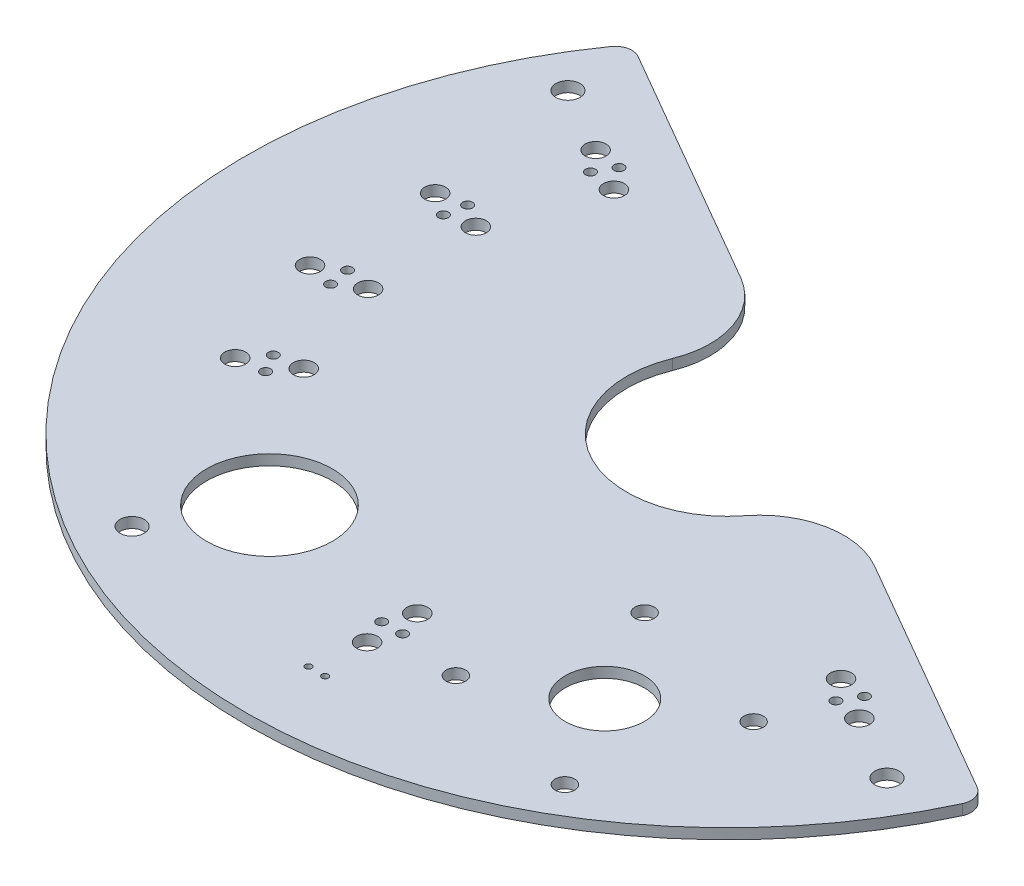
SolidWorks part; units mm, degrees
ref_plane "Front Plane" through (0, 0, 0) normal (0, 0, 1) x (1, 0, 0)
ref_plane "Top Plane" through (0, 0, 0) normal (0, 1, 0) x (1, 0, 0)
ref_plane "Right Plane" through (0, 0, 0) normal (1, 0, 0) x (0, 0, -1)
sketch "Sketch1" plane through (0, 0, 0) normal (0, 1, 0) x (1, 0, 0)
  line L0 (0, 50.8) -> (0, 59.6199) construction
  line L1 (0, 50.8) -> (11.3081, 50.8) construction
  line L2 (0, 0) -> (0, 47) construction
  line L3 (0, 0) -> (-46.286, 8.1615) construction
  line L4 (0, 0) -> (0, 47) construction
  line L5 (0, 0) -> (-46.286, -8.1615) construction
  circle A0 centre (0, 0) radius 50.8 construction
  circle A1 centre (0, 0) radius 15.24
  circle A2 centre (0, 0) radius 73.025
  circle A3 centre (0, 50.8) radius 6.3 construction
  circle A4 centre (25.4, 43.9941) radius 6.3 construction
  circle A5 centre (43.9941, 25.4) radius 6.3 construction
  circle A6 centre (50.8, 0) radius 6.3 construction
  circle A7 centre (43.9941, -25.4) radius 6.3 construction
  circle A8 centre (25.4, -43.9941) radius 6.3 construction
  circle A9 centre (0, -50.8) radius 6.3 construction
  circle A10 centre (-25.4, -43.9941) radius 6.3 construction
  circle A11 centre (-43.9941, -25.4) radius 6.3 construction
  circle A12 centre (-50.8, 0) radius 6.3 construction
  circle A13 centre (-43.9941, 25.4) radius 6.3 construction
  circle A14 centre (-25.4, 43.9941) radius 6.3 construction
  circle A15 centre (0, 50.8) radius 1.585 construction
  circle A16 centre (-1.585, 50.8) radius 0.75
  circle A17 centre (1.585, 50.8) radius 0.75
  circle A18 centre (0, 50.8) radius 3.8 construction
  circle A19 centre (0, 54.6) radius 1.585
  circle A20 centre (0, 47) radius 1.585
  circle A21 centre (47.285, 27.3) radius 1.585
  circle A22 centre (43.2016, 26.7727) radius 0.75
  circle A23 centre (44.7866, 24.0273) radius 0.75
  circle A24 centre (40.7032, 23.5) radius 1.585
  circle A25 centre (47.285, -27.3) radius 1.585
  circle A26 centre (44.7866, -24.0273) radius 0.75
  circle A27 centre (43.2016, -26.7727) radius 0.75
  circle A28 centre (40.7032, -23.5) radius 1.585
  circle A29 centre (0, -54.6) radius 1.585
  circle A30 centre (1.585, -50.8) radius 0.75
  circle A31 centre (-1.585, -50.8) radius 0.75
  circle A32 centre (0, -47) radius 1.585
  circle A33 centre (-47.285, -27.3) radius 1.585
  circle A34 centre (-43.2016, -26.7727) radius 0.75
  circle A35 centre (-44.7866, -24.0273) radius 0.75
  circle A36 centre (-40.7032, -23.5) radius 1.585
  circle A37 centre (-47.285, 27.3) radius 1.585
  circle A38 centre (-44.7866, 24.0273) radius 0.75
  circle A39 centre (-43.2016, 26.7727) radius 0.75
  circle A40 centre (-40.7032, 23.5) radius 1.585
  circle A41 centre (25.4, 43.9941) radius 20
  circle A42 centre (-25.4, -43.9941) radius 9.525
  circle A43 centre (25.4, -43.9941) radius 6
  circle A44 centre (-46.286, 8.1615) radius 1.585
  circle A45 centre (-50.3035, 7.2604) radius 0.75
  circle A46 centre (-49.753, 10.3822) radius 0.75
  circle A47 centre (-53.7705, 9.4812) radius 1.585
  circle A48 centre (-46.286, -8.1615) radius 1.585
  circle A49 centre (-49.753, -10.3822) radius 0.75
  circle A50 centre (-50.3035, -7.2604) radius 0.75
  circle A51 centre (-53.7705, -9.4812) radius 1.585
  point P50 (0, 0)
  point P84 (0, 0)
  dimension "D1" = 12
  dimension "D2" = 101.6
  dimension "D3" = 3.17
  dimension "D4" = 1.5
  dimension "D5" = 7.6
  dimension "D6" = 6
  dimension "D7" = 3.17
  dimension "D8" = 40
  dimension "D9" = 19.05
  dimension "D10" = 12
  dimension "D11" = 146.05
  dimension "D12" = 30.48
  dimension "D14" = 80
  dimension "D16" = 100
  dimension "D13" = 2
  dimension "D15" = 2
extrude "Boss-Extrude1" add sketch "Sketch1" against normal blind 1.5875
sketch "Sketch2" plane through (0, 0, 0) normal (0, 1, 0) x (1, 0, 0)
  line L0 (0, 0) -> (0, 66.04) construction
  line L1 (0, 0) -> (-57.1923, 33.02) construction
  circle A0 centre (0, 0) radius 66.04 construction
  circle A1 centre (0, 66.04) radius 1.8288 construction
  circle A2 centre (-57.1923, 33.02) radius 1.8288
  circle A3 centre (33.02, 57.1923) radius 1.8288
  circle A4 centre (57.1923, -33.02) radius 1.8288
  circle A5 centre (-33.02, -57.1923) radius 1.8288
  point P17 (0, 0)
  dimension "D1" = 132.08
  dimension "D2" = 3.6576
  dimension "D3" = 2
  dimension "D4" = 60
  dimension "D5" = 4
extrude "Cut-Extrude1" cut sketch "Sketch2" against normal through all
sketch "Sketch3" plane through (0, 0, 0) normal (0, 1, 0) x (1, 0, 0)
  line L0 (-57.1923, 33.02) -> (57.1923, -33.02) construction
  line L1 (-59.5338, 44.6372) -> (68.4238, -29.2392)
  line L2 (-52.7473, 40.719) -> (61.6373, -25.321) construction
  arc A0 (68.4238, -29.2392) -> (-59.5338, 44.6372) centre (0, 0) ccw
  dimension "D1" = 8.89
extrude "Cut-Extrude2" cut sketch "Sketch3" against normal through all
fillet "Fillet1" radius 12.7 2 edges at (15.165, -0.7937, -1.5098) (-6.275, -0.7937, -13.8882)
fillet "Fillet2" radius 2.54 2 edges at (67.2161, -0.7937, 28.542) (-58.3261, -0.7937, -43.9399)
sketch "Sketch4" plane through (0, 0, 0) normal (0, 1, 0) x (1, 0, 0)
  line L0 (0, 0) -> (0, -73.025) construction
  arc A0 (-59.6949, 42.0615) -> (66.2738, -30.6666) centre (0, 0) ccw construction
  circle A1 centre (0, 0) radius 62.23 construction
  circle A2 centre (0, -62.23) radius 0.4953 construction
  circle A3 centre (1.27, -62.23) radius 0.4953
  circle A4 centre (-1.27, -62.23) radius 0.4953
  dimension "D1" = 0.9906
  dimension "D4" = 124.46
  dimension "D2" = 2
  dimension "D3" = 2
extrude "Cut-Extrude3" cut sketch "Sketch4" against normal through all
sketch "Sketch5" plane through (0, -1.5875, 0) normal (0, -1, 0) x (1, 0, 0)
  line L13 (30.4135, 24.5983) -> (41.5359, 31.0198)
  line L14 (28.0125, 9.134) -> (57.5769, 26.203)
  line L29 (46.7892, 22.3211) -> (54.9392, 27.0264)
  line L30 (29.0803, 12.0968) -> (45.0238, 21.3018)
  line L31 (6.096, 38.6381) -> (6.096, 51.4811)
  line L32 (29.8903, 21.9498) -> (40.9598, 28.3409)
  line L33 (-6.096, 38.6381) -> (-6.096, 51.4811)
  line L34 (4.064, 36.8606) -> (4.064, 49.6426)
  line L35 (-21.9165, -19.6925) -> (-41.5359, -31.0198)
  line L39 (-4.064, 36.8606) -> (-4.064, 49.6426)
  line L40 (-30.4135, 24.5983) -> (-41.5359, 31.0198)
  line L42 (-29.8903, 21.9498) -> (-40.9598, 28.3409)
  line L93 (-25.0163, -19.1359) -> (-40.9598, -28.3409)
  line L98 (-46.7892, 22.3211) -> (-54.9392, 27.0264)
  line L99 (-47.6319, 20.4612) -> (-57.5769, 26.203)
  arc A0 (1.2907, 63.2458) -> (1.2493, 61.2142) centre (1.27, 62.23) ccw
  arc A1 (-1.2493, 61.2142) -> (-1.2907, 63.2458) centre (-1.27, 62.23) ccw
  arc A2 (-1.2493, 61.2142) -> (-54.9392, 27.0264) centre (0, 0) ccw
  arc A3 (-1.2907, 63.2458) -> (-57.5769, 26.203) centre (0, 0) ccw
  arc A4 (54.9392, 27.0264) -> (1.2493, 61.2142) centre (0, 0) ccw
  arc A6 (6.096, 51.4811) -> (2.3857, 51.7858) centre (0, 0) ccw
  arc A7 (29.8903, 21.9498) -> (4.064, 36.8606) centre (0, 0) ccw
  arc A8 (2.3857, 51.7858) -> (2.3071, 49.7553) centre (1.585, 50.8) ccw
  arc A9 (-2.3071, 49.7553) -> (-2.3857, 51.7858) centre (-1.585, 50.8) ccw
  arc A10 (-48.5987, -10.912) -> (-50.5848, -11.342) centre (-49.753, -10.3822) ccw
  arc A11 (-51.4133, -6.6431) -> (-49.4, -6.3679) centre (-50.3035, -7.2604) ccw
  arc A12 (46.0407, 23.8268) -> (44.2429, 22.8796) centre (44.7866, 24.0273) ccw
  arc A13 (41.9358, 26.8756) -> (43.655, 27.959) centre (43.2016, 26.7727) ccw
  arc A14 (-49.4, 6.3679) -> (-51.4133, 6.6431) centre (-50.3035, 7.2604) ccw
  arc A15 (-50.5848, 11.342) -> (-48.5987, 10.912) centre (-49.753, 10.3822) ccw
  arc A16 (57.5769, 26.203) -> (1.2907, 63.2458) centre (0, 0) ccw
  arc A17 (-2.3857, 51.7858) -> (-6.096, 51.4811) centre (0, 0) ccw
  arc A18 (-2.3071, 49.7553) -> (-4.064, 49.6426) centre (0, 0) ccw
  arc A19 (45.0238, 21.3018) -> (44.2429, 22.8796) centre (0, 0) ccw
  arc A20 (29.0803, 12.0968) -> (-25.0163, -19.1359) centre (0, 0) ccw
  arc A21 (28.0125, 9.134) -> (-21.9165, -19.6925) centre (0, 0) ccw
  arc A22 (46.7892, 22.3211) -> (46.0407, 23.8268) centre (0, 0) ccw
  arc A23 (43.655, 27.959) -> (41.5359, 31.0198) centre (0, 0) ccw
  arc A24 (-46.0407, -23.8268) -> (-44.2429, -22.8796) centre (-44.7866, -24.0273) ccw
  arc A25 (-41.9358, -26.8756) -> (-43.655, -27.959) centre (-43.2016, -26.7727) ccw
  arc A26 (41.9358, 26.8756) -> (40.9598, 28.3409) centre (0, 0) ccw
  circle A27 centre (1.27, 62.23) radius 0.4953
  arc A28 (-43.655, 27.959) -> (-41.9358, 26.8756) centre (-43.2016, 26.7727) ccw
  arc A29 (-44.2429, 22.8796) -> (-46.0407, 23.8268) centre (-44.7866, 24.0273) ccw
  circle A30 centre (-1.27, 62.23) radius 0.4953
  arc A31 (-43.655, -27.959) -> (-41.5359, -31.0198) centre (0, 0) ccw
  circle A32 centre (-26.7727, 43.2016) radius 1.27 [skipped]
  circle A33 centre (-24.0273, 44.7866) radius 1.27 [skipped]
  circle A34 centre (24.0273, 44.7866) radius 1.27 [skipped]
  circle A35 centre (26.7727, 43.2016) radius 1.27 [skipped]
  circle A36 centre (50.8, 1.585) radius 1.27 [skipped]
  circle A37 centre (50.8, -1.585) radius 1.27 [skipped]
  circle A38 centre (44.7866, -24.0273) radius 1.27 [skipped]
  circle A39 centre (43.2016, -26.7727) radius 1.27 [skipped]
  circle A40 centre (26.7727, -43.2016) radius 1.27 [skipped]
  circle A41 centre (24.0273, -44.7866) radius 1.27 [skipped]
  circle A42 centre (1.585, -50.8) radius 1.27 [skipped]
  circle A43 centre (-1.585, -50.8) radius 1.27 [skipped]
  circle A44 centre (-24.0273, -44.7866) radius 1.27 [skipped]
  circle A45 centre (-26.7727, -43.2016) radius 1.27 [skipped]
  circle A46 centre (-50.8, 1.585) radius 1.27 [skipped]
  circle A47 centre (-50.8, -1.585) radius 1.27 [skipped]
  arc A48 (-41.9358, -26.8756) -> (-40.9598, -28.3409) centre (0, 0) ccw
  arc A49 (-40.9598, 28.3409) -> (-41.9358, 26.8756) centre (0, 0) ccw
  arc A50 (30.4135, 24.5983) -> (6.096, 38.6381) centre (0, 0) ccw
  circle A51 centre (1.585, 50.8) radius 0.75
  arc A52 (-46.0407, 23.8268) -> (-46.7892, 22.3211) centre (0, 0) ccw
  arc A53 (4.064, 49.6426) -> (2.3071, 49.7553) centre (0, 0) ccw
  arc A54 (-41.5359, 31.0198) -> (-43.655, 27.959) centre (0, 0) ccw
  arc A55 (-6.096, 38.6381) -> (-30.4135, 24.5983) centre (0, 0) ccw
  arc A56 (-4.064, 36.8606) -> (-29.8903, 21.9498) centre (0, 0) ccw
  arc A57 (-44.2429, 22.8796) -> (-48.5987, 10.912) centre (0, 0) ccw
  circle A58 centre (-1.585, 50.8) radius 0.75
  circle A59 centre (43.2016, 26.7727) radius 0.75
  arc A60 (-47.6319, 20.4612) -> (-50.5848, 11.342) centre (0, 0) ccw
  arc A61 (-51.4133, 6.6431) -> (-51.4133, -6.6431) centre (0, 0) ccw
  arc A62 (-49.4, 6.3679) -> (-49.4, -6.3679) centre (0, 0) ccw
  circle A63 centre (44.7866, 24.0273) radius 0.75
  arc A64 (-50.5848, -11.342) -> (-46.0407, -23.8268) centre (0, 0) ccw
  arc A65 (-48.5987, -10.912) -> (-44.2429, -22.8796) centre (0, 0) ccw
  circle A66 centre (-43.2016, 26.7727) radius 0.75
  circle A67 centre (-44.7866, 24.0273) radius 0.75
  circle A68 centre (-49.753, 10.3822) radius 0.75
  circle A69 centre (-50.3035, 7.2604) radius 0.75
  circle A70 centre (-50.3035, -7.2604) radius 0.75
  circle A71 centre (-49.753, -10.3822) radius 0.75
  circle A72 centre (-44.7866, -24.0273) radius 0.75
  circle A73 centre (-43.2016, -26.7727) radius 0.75
  dimension "D13" = 12
  dimension "D15" = 3
extrude "Boss-Extrude2" add sketch "Sketch5" along normal blind 0.1016
sketch "Sketch6" plane through (0, -1.5875, 0) normal (0, -1, 0) x (1, 0, 0)
  line L0 (0, 0) -> (25.4, 43.9941) construction
  line L1 (25.4, 43.9941) -> (36.5125, 63.2415) construction
  circle A0 centre (25.4, 43.9941) radius 16.51 construction
  arc A1 (66.2738, 30.6666) -> (-59.6949, -42.0615) centre (0, 0) ccw construction
  circle A2 centre (33.655, 58.2922) radius 1.4732
  circle A3 centre (11.1019, 52.2491) radius 1.4732
  circle A4 centre (17.145, 29.696) radius 1.4732
  circle A5 centre (39.6981, 35.7391) radius 1.4732
  point P20 (25.4, 43.9941)
  dimension "D1" = 2.9464
extrude "Cut-Extrude4" cut sketch "Sketch6" against normal through all
